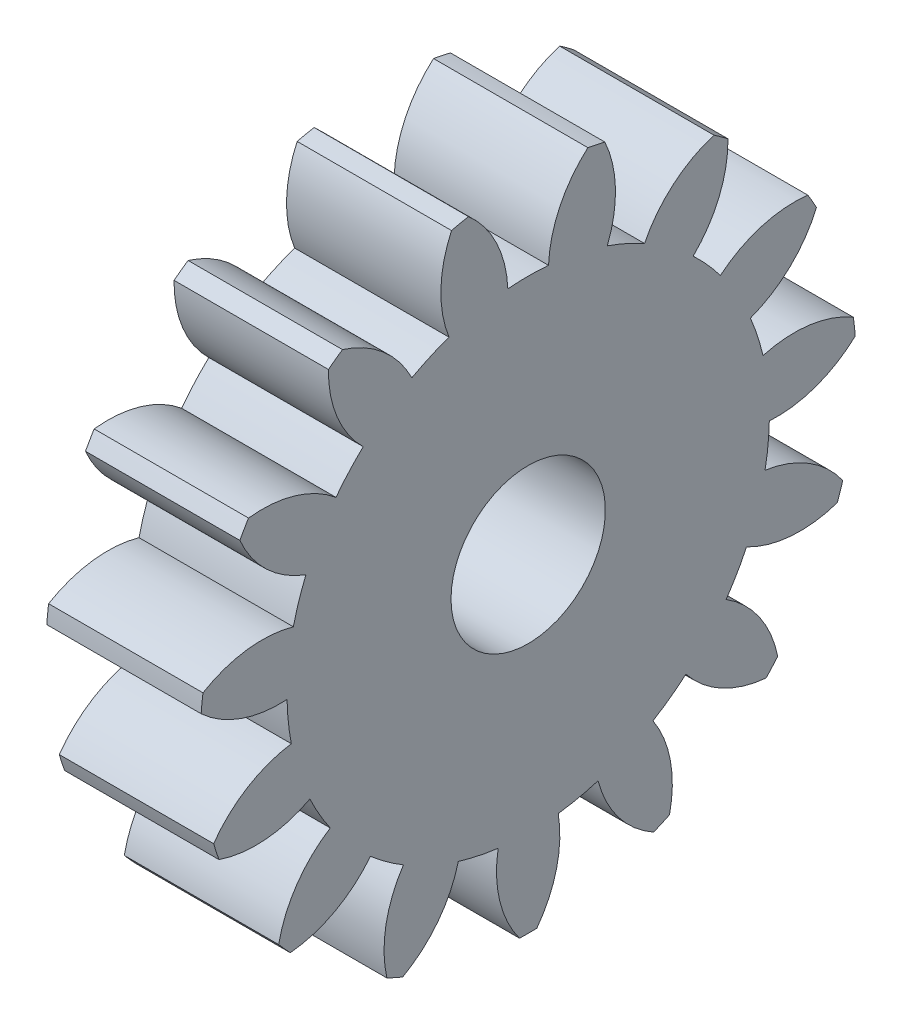
SolidWorks part; units mm, degrees
ref_plane "Plane1" through (0, 0, 0) normal (0, 0, 1) x (1, 0, 0)
ref_plane "Plane2" through (0, 0, 0) normal (0, 1, 0) x (1, 0, 0)
ref_plane "Plane3" through (0, 0, 0) normal (1, 0, 0) x (0, 0, -1)
sketch "HoldingSke" plane through (0, 0, 0) normal (0, 1, 0) x (1, 0, 0)
  line L0 (0, 0) -> (0.644, -0.1725)
  line L1 (-15, 0) -> (100, 0) construction
  line L2 (0, 0) -> (-2.1039, 2.3779)
  line L3 (0, 0) -> (-11.863, 4.5341)
  line L4 (0, 0) -> (8.3417, 2.2352)
  line L5 (0, 0) -> (-46.8476, -17.4728)
  line L6 (0, 0) -> (-4.9738, -3.3558)
  line L7 (-2.1039, 2.3779) -> (8.6586, 51.2059)
  line L8 (-76.2, 54.61) -> (-75.2, 54.61)
  line L9 (-71.009, 38.7566) -> (-53.1078, 45.2721)
  line L10 (-76.2, 71.12) -> (104.1128, 71.12)
  line L11 (0, 0) -> (-6, 0)
  line L12 (-76.2, 101.6) -> (-76.147, 101.6)
  line L13 (24.9733, 27.94) -> (52.9518, 28.4284)
  line L14 (24.9733, 27.94) -> (24.9743, 27.94)
  line L15 (24.9733, 27.94) -> (100.4006, 29.5858)
  line L16 (-63.627, -1.5) -> (-12.827, -1.5)
  circle A0 centre (0, 0) radius 3
  circle A1 centre (0, 0) radius 9.374
  circle A2 centre (0, 0) radius 37.5
  circle A3 centre (0, 0) radius 3
  dimension "Num_teeth" = 15
  dimension "Pitch_radius" = 180.3128
  dimension "Width" = 6
  dimension "Thickness" = 6
sketch "BasProSke" plane through (0, 0, 0) normal (0, 1, 0) x (1, 0, 0)
  line L0 (-10, 0) -> (60, 0) construction
  line L1 (0, 0) -> (0, 12.75)
  line L2 (0, 0) -> (6, 0)
  line L3 (6, 0) -> (6, 12.75)
  line L4 (6, 12.75) -> (0, 12.75)
  dimension "Thickness" = 6
  dimension "Diameter" = 25.5
revolve "Base-Revolve" add sketch "BasProSke" angle 360 about L0
sketch "TooCutSke" plane through (0, 0, 0) normal (1, 0, 0) x (0, 0, -1)
  line L1 (0, 0) -> (0, 107) construction
  line L2 (0, 0) -> (-1.2686, 11.1782) construction
  line L3 (0, 0) -> (-4.6563, 21.9061) construction
  line L4 (-1.2686, 11.1782) -> (-2.3281, 10.953) construction
  arc A0 (0.7915, 9.3405) -> (-0.7915, 9.3405) centre (0, 0) ccw
  arc A1 (2.3447, 12.5584) -> (-2.3447, 12.5584) centre (0, 0) ccw
  circle A2 centre (0, 0) radius 11.25 construction
  circle A3 centre (0, 0) radius 10.5715 construction
  arc A4 (-0.7915, 9.3405) -> (-2.3447, 12.5584) centre (-5.2877, 9.1541) ccw
  arc A5 (2.3447, 12.5584) -> (0.7915, 9.3405) centre (5.2877, 9.1541) ccw
extrude "ToothCut" cut sketch "TooCutSke" along normal through all
fillet "Breaks" [suppressed] radius 0.03 tangent propagation no
fillet "RootFillets" [suppressed] radius 0.376
pattern_circular "TeethCuts" count 15 every 24 about axis through (-10, 0, 0) along (1, 0, 0) of "ToothCut", "RootFillets", "Breaks"
sketch "HubNeaOneSke" plane through (0, 0, 0) normal (-1, 0, 0) x (0, 0, 1)
  circle A0 centre (0, 0) radius 9.374
  dimension "Diameter" = 18.748
extrude "HubNearOne" [suppressed] add sketch "HubNeaOneSke" along normal blind 44.0001
sketch "HubNeaBotSke" plane through (0, 0, 0) normal (-1, 0, 0) x (0, 0, 1)
  circle A0 centre (0, 0) radius 9.374
  dimension "Diameter" = 18.748
extrude "HubNearBoth" [suppressed] add sketch "HubNeaBotSke" along normal blind 22
ref_plane "FarPln" through (6, 0, 0) normal (1, 0, 0) x (0, 0, -1)
sketch "HubFarSke" plane through (6, 0, 0) normal (1, 0, 0) x (0, 0, -1)
  circle A0 centre (0, 0) radius 9.374
  dimension "Diameter" = 18.748
extrude "HubFar" [suppressed] add sketch "HubFarSke" along normal blind 22
sketch "BorSke" plane through (0, 0, 0) normal (1, 0, 0) x (0, 0, -1)
  circle A0 centre (0, 0) radius 3
  dimension "Diameter" = 6
extrude "Bore" cut sketch "BorSke" along normal mid plane 100.0001
sketch "KeySke" plane through (0, 0, 0) normal (1, 0, 0) x (0, 0, -1)
  line L0 (-1, 0) -> (-1, 4)
  line L1 (-1, 4) -> (1, 4)
  line L2 (1, 4) -> (1, 0)
  line L3 (0, 0) -> (0, 34) construction
  line L4 (-1, 0) -> (1, 0)
  dimension "Width" = 2
extrude "Keyway" [suppressed] cut sketch "KeySke" along normal mid plane 100.0001
pattern_circular "Keyway2" [suppressed] count 2 every 90 about axis through (-10, 0, 0) along (1, 0, 0) reverse direction yes
sketch "Sketch1" plane through (6, 0, 0) normal (1, 0, 0) x (0, 0, -1)
  circle A0 centre (0, 0) radius 3
  circle A1 centre (0, 0) radius 6.3275
  dimension "D1" = 6
  dimension "D2" = 12.6549
equation "' \"Module@HoldingSke\" = 6.35"
equation "' \"Num_teeth@HoldingSke\" = 12"
equation "' \"Ap@HoldingSke\" =  20"
equation "' \"Ap@HoldingSke\" = 20"
equation "' \"Width@HoldingSke\" = 0.5 * 25.4"
equation "' \"Hub_dia@HoldingSke\"= 1 * 25.4"
equation "' \"Hub_dia@HoldingSke\" = 1 * 25.4"
equation "' \"Overall_len@HoldingSke\" = 1.0 * 25.4"
equation "' \"Bore@HoldingSke\" = 0.75 * 25.4"
equation "' \"T_dim@HoldingSke\" = 0.1 * 25.4"
equation "' \"Width@KeySke\" = 0.25 * 25.4"
equation "' \"Show_teeth@HoldingSke\" = 13"
equation "' \"Backlash@HoldingSke\" = 0.009 * 25.4"
equation "' \"Addendum_fac@HoldingSke\" = 1.0"
equation "' \"Dedendum_fac@HoldingSke\" = 1.25"
equation "' \"Dedendum_add@HoldingSke\" = 0.00005 * 25.4"
equation "' \"Clearance_fac@HoldingSke\" = 0.25"
equation "\"Pitch@HoldingSke\" = 1 / \"Module@HoldingSke\""
equation "\"Overcut_dia@TooCutSke\" = (\"Num_teeth@HoldingSke\" + 2 * \"Addendum_fac@HoldingSke\") / \"Pitch@HoldingSke\" + 0.002 * 25.4"
equation "\"Pitch_dia@TooCutSke\" = \"Num_teeth@HoldingSke\" / \"Pitch@HoldingSke\""
equation "\"Base_dia@TooCutSke\" = \"Num_teeth@HoldingSke\" / \"Pitch@HoldingSke\" * cos((\"Ap@HoldingSke\"  * 3.14159265 / 180))"
equation "\"Root_dia@TooCutSke\" = (\"Num_teeth@HoldingSke\" + 2) / \"Pitch@HoldingSke\" - 2 * (\"Addendum_fac@HoldingSke\" + \"Dedendum_fac@HoldingSke\") / \"Pitch@HoldingSke\" - \"Dedendum_add@HoldingSke\" * 2"
equation "\"Half_ang@TooCutSke\" = 180 / \"Num_teeth@HoldingSke\""
equation "\"Half_CT@TooCutSke\" = \"Num_teeth@HoldingSke\" / \"Pitch@HoldingSke\" * sin((3.14159265 / 2 / \"Num_teeth@HoldingSke\")) / 2 - 7 * \"Backlash@HoldingSke\" / 4"
equation "\"Flank_rad@TooCutSke\" = \"Num_teeth@HoldingSke\" / \"Pitch@HoldingSke\" / 5"
equation "\"Radius@RootFillets\" = \"Clearance_fac@HoldingSke\" / \"Pitch@HoldingSke\" + \"Dedendum_add@HoldingSke\""
equation "\"Break_rad@Breaks\" = 0.02 / \"Pitch@HoldingSke\""
equation "\"Thickness@HoldingSke\" = \"Width@HoldingSke\""
equation "\"OAL@HoldingSke\" = \"Thickness@HoldingSke\""
equation "\"MHD@HoldingSke\" = (\"Num_teeth@HoldingSke\" + 2) / \"Pitch@HoldingSke\" - 2 * (\"Addendum_fac@HoldingSke\" + \"Dedendum_fac@HoldingSke\")  / \"Pitch@HoldingSke\" - \"Dedendum_add@HoldingSke\" * 2"
equation "\"MBD@HoldingSke\" = (\"Num_teeth@HoldingSke\" + 2) / \"Pitch@HoldingSke\" - 2 * (\"Addendum_fac@HoldingSke\" + \"Dedendum_fac@HoldingSke\")  / \"Pitch@HoldingSke\" - \"Dedendum_add@HoldingSke\" * 2 - 0.002 * 25.4"
equation "\"MHD@HoldingSke\" = ((sgn( \"MHD@HoldingSke\" - \"Hub_dia@HoldingSke\" )-1)*( \"MHD@HoldingSke\" - \"Hub_dia@HoldingSke\" ))/-2+ \"Hub_dia@HoldingSke\""
equation "\"MBD@HoldingSke\" = ((sgn( \"MBD@HoldingSke\" - \"Bore@HoldingSke\" )-1)*( \"MBD@HoldingSke\" - \"Bore@HoldingSke\" ))/-2+ \"Bore@HoldingSke\""
equation "\"OAL@HoldingSke\" = ((sgn( \"OAL@HoldingSke\" - \"Overall_len@HoldingSke\" )+1)*( \"OAL@HoldingSke\" - \"Overall_len@HoldingSke\" ))/2 + \"Overall_len@HoldingSke\" + 0.000002 * 25.4"
equation "\"Num_teeth@TeethCuts\" = int( \"Show_teeth@HoldingSke\" ) + 1"
equation "\"Num_teeth@TeethCuts\" = ((sgn( \"Num_teeth@TeethCuts\" - \"Num_teeth@HoldingSke\" )-1)*( \"Num_teeth@TeethCuts\" - \"Num_teeth@HoldingSke\" ))/-2+ \"Num_teeth@HoldingSke\""
equation "\"Num_teeth@TeethCuts\" = ((sgn( \"Num_teeth@TeethCuts\" - 2.0)+1)*( \"Num_teeth@TeethCuts\" - 2.0))/2 +2.0"
equation "\"Angle@TeethCuts\" = 360.0 / \"Num_teeth@HoldingSke\""
equation "\"Diameter@BasProSke\" = (\"Num_teeth@HoldingSke\" + 2 * \"Addendum_fac@HoldingSke\") / \"Pitch@HoldingSke\""
equation "\"Thickness@BasProSke\"  = \"Thickness@HoldingSke\""
equation "' \"Fillet_rad@BasProSke\" =  \"Thickness@HoldingSke\" * 0.05"
equation "' \"Fillet_rad@BasProSke\" = \"Thickness@HoldingSke\" * 0.05"
equation "\"MHD@HoldingSke\" = ((sgn( \"MHD@HoldingSke\" - \"Root_dia@TooCutSke\" )-1)*( \"MHD@HoldingSke\" - \"Root_dia@TooCutSke\" ))/-2+ \"Root_dia@TooCutSke\""
equation "\"Diameter@HubNeaOneSke\" = \"MHD@HoldingSke\""
equation "\"Length@HubNearOne\" = \"OAL@HoldingSke\" - \"Thickness@BasProSke\""
equation "\"Diameter@HubNeaBotSke\" = \"MHD@HoldingSke\""
equation "\"Length@HubNearBoth\" = ( \"OAL@HoldingSke\" - \"Thickness@BasProSke\" ) / 2.0"
equation "\"Thickness@FarPln\" = \"Thickness@BasProSke\""
equation "\"Diameter@HubFarSke\" = \"MHD@HoldingSke\""
equation "\"Length@HubFar\" = ( \"OAL@HoldingSke\" - \"Thickness@BasProSke\" ) / 2.0"
equation "\"Diameter@BorSke\" = \"MBD@HoldingSke\""
equation "\"D1@Bore\" = \"OAL@HoldingSke\" * 2.0"
equation "\"D1@Keyway\" = \"OAL@HoldingSke\" * 2.0"
equation "\"Offset@KeySke\" = \"T_dim@HoldingSke\" + \"MBD@HoldingSke\" / 2.0"
